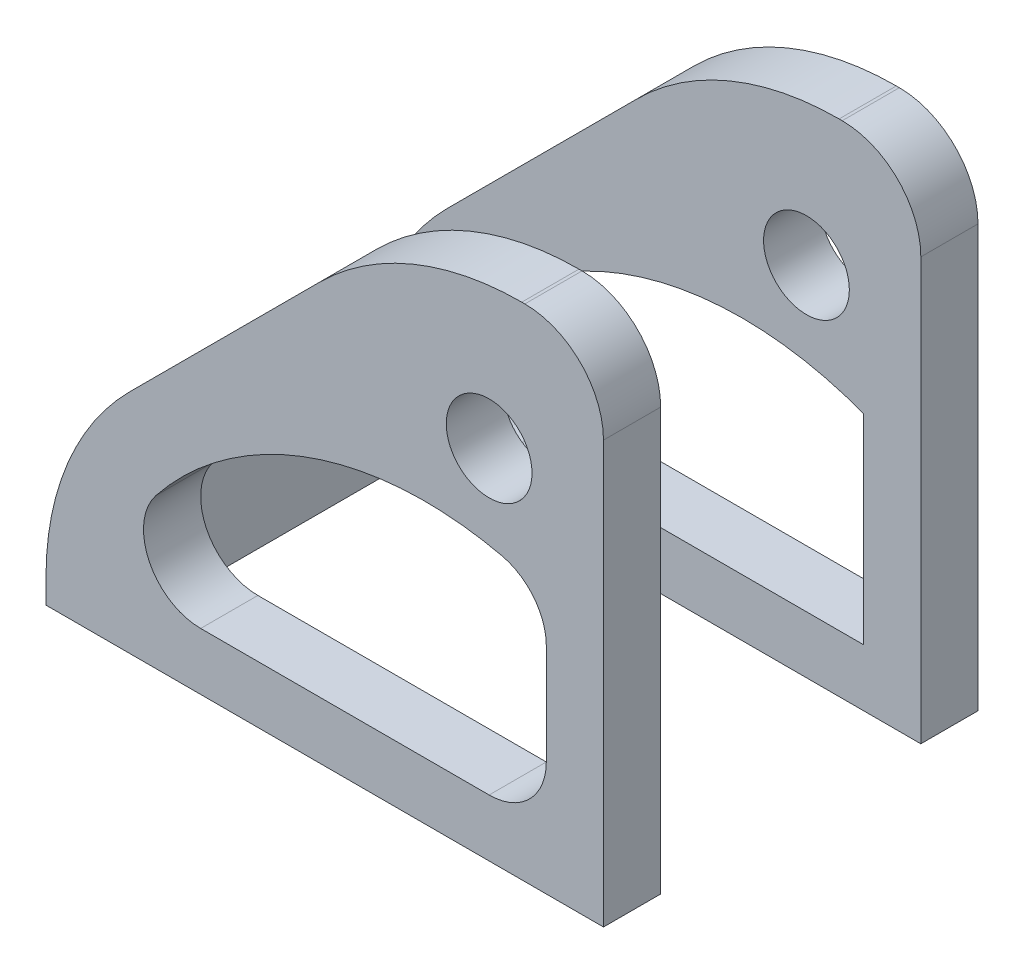
SolidWorks part; units mm, degrees
ref_plane "Front Plane" through (0, 0, 0) normal (0, 0, 1) x (1, 0, 0)
ref_plane "Top Plane" through (0, 0, 0) normal (0, 1, 0) x (1, 0, 0)
ref_plane "Right Plane" through (0, 0, 0) normal (1, 0, 0) x (0, 0, -1)
sketch "Sketch3" plane through (0, 0, 0) normal (0, 1, 0) x (1, 0, 0)
  line L0 (39, -13.1) -> (39, -9.1)
  line L1 (39, -9.1) -> (4, -9.1)
  line L2 (4, -9.1) -> (4, 9.1)
  line L4 (39, -13.1) -> (0, -13.1)
  line L5 (0, -13.1) -> (0, 13.1)
  line L6 (0, 0) -> (-50000, 0) construction
  line L7 (39, 13.1) -> (39, 9.1)
  line L8 (39, 13.1) -> (0, 13.1)
  line L9 (39, 9.1) -> (4, 9.1)
  point P3 (0, 0)
  point P4 (0, 0)
  dimension "D1" = 4
  dimension "D2" = 4
  dimension "D3" = 9.1
  dimension "D4" = 35
extrude "Boss-Extrude1" add sketch "Sketch3" along normal blind 35
sketch "Sketch4" plane through (0, 0, 0) normal (0, 0, 1) x (1, 0, 0)
  line L0 (-17.0868, 0) -> (49982.9132, 0) construction
  line L1 (-1.0986, 28) -> (49998.9014, 28) construction
  line L2 (1.4906, 22) -> (50001.4906, 22) construction
  line L3 (34, -3.2504) -> (34, -50003.2504) construction
  line L6 (0, 0) -> (39, 0) construction
  line L9 (4, 35) -> (4, 0) construction
  circle A0 centre (31, 25) radius 3
  circle A1 centre (31, 15) radius 15 construction
  point P12 (23.0197, 26.5063)
  point P15 (33.0118, 25)
  dimension "D1" = 6
  dimension "D3" = 30
  dimension "D2" = 7
  dimension "D4" = 30
extrude "Cut-Extrude1" cut sketch "Sketch4" against normal through all both and the other way through all contours A0
chamfer "Chamfer1" distance 25 angle 45 1 edges at (0, 35, 0)
fillet "Fillet1" radius 20 3 edges at (0, 10, 0) (25, 35, -11.1) (25, 35, 11.1)
fillet "Fillet2" radius 5.5 2 edges at (39, 35, -11.1) (39, 35, 11.1)
fillet "Fillet3" radius 1 1 edges at (4, 13.7157, 0)
sketch "Sketch5" plane through (0, 0, 13.1) normal (0, 0, 1) x (1, 0, 0)
  line L0 (39, 29.5) -> (39, 0) construction
  line L1 (4, 4) -> (35, 4)
  line L2 (4, 4) -> (4, 18) construction
  line L3 (4, 18) -> (35, 18) construction
  line L4 (35, 4) -> (35, 18) construction
  line L5 (0, 0) -> (39, 0) construction
  line L6 (29.2128, 22) -> (50029.2128, 22) construction
  line L7 (4, 4) -> (26.5, -4.5) construction
  line L8 (26.5, -4.5) -> (35, 18) construction
  line L9 (35, 18) -> (35, 4)
  arc A0 (4, 4) -> (35, 18) centre (26.5, -4.5) cw
  circle A1 centre (31, 25) radius 3 construction
  dimension "D1" = 4
  dimension "D2" = 4
  dimension "D3" = 4
  dimension "D4" = 4
extrude "Cut-Extrude2" cut sketch "Sketch5" against normal through all both and the other way through all
fillet "Fillet4" radius 4 4 edges at (35, 18, 11.1) (35, 4, 11.1) (4, 4, 11.1)
